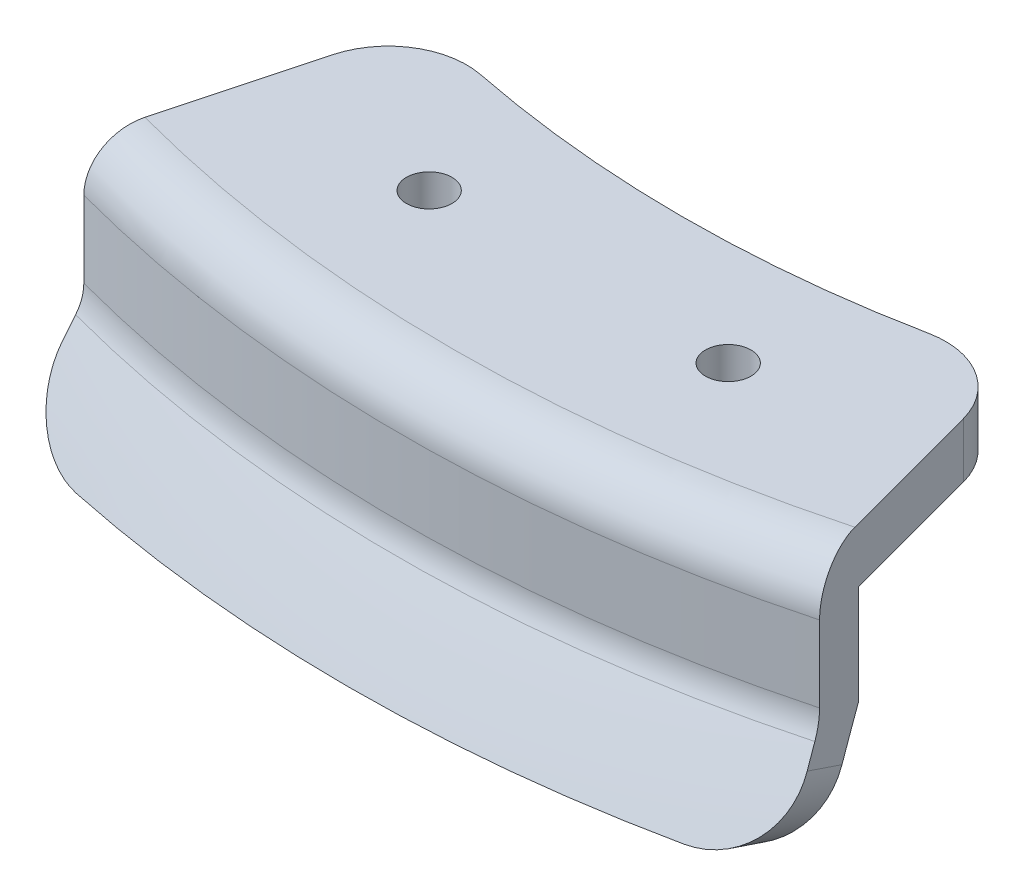
SolidWorks part; units mm, degrees
material "Polyether Polyol"
ref_plane "Front Plane" through (0, 0, 0) normal (0, 0, 1) x (1, 0, 0)
ref_plane "Top Plane" through (0, 0, 0) normal (0, 1, 0) x (1, 0, 0)
ref_plane "Right Plane" through (0, 0, 0) normal (1, 0, 0) x (0, 0, -1)
sketch "Sketch2" plane through (0, 0, 0) normal (1, 0, 0) x (0, 0, -1)
  line L0 (-174.1012, 207.3685) -> (-174.1012, 194.6685) construction
  line L1 (-188.0743, 183.7605) -> (-181.8111, 180.6344) construction
  line L2 (-181.1012, 214.3685) -> (-181.1012, 196.5948) construction
  line L3 (-181.1012, 214.3685) -> (-145.5262, 214.3685) construction
  line L4 (-145.5262, 214.3685) -> (-145.5262, 207.3685) construction
  line L5 (-145.5262, 207.3685) -> (-174.1012, 207.3685) construction
  line L12 (0, 89.8878) -> (0, 207.3685) construction
  line L13 (-174.1012, 207.3685) -> (-174.1012, 194.6685)
  line L14 (-188.0743, 183.7605) -> (-181.8111, 180.6344)
  line L15 (-181.1012, 214.3685) -> (-181.1012, 196.5948)
  line L16 (-181.1012, 214.3685) -> (-145.5262, 214.3685)
  line L17 (-145.5262, 214.3685) -> (-145.5262, 207.3685)
  line L18 (-145.5262, 207.3685) -> (-174.1012, 207.3685)
  arc A0 (-174.1012, 194.6685) -> (-181.8111, 180.6344) centre (0, 89.8878) ccw construction
  arc A1 (-181.1012, 196.5948) -> (-188.0743, 183.7605) centre (0, 89.8878) ccw construction
  arc A4 (-174.1012, 194.6685) -> (-181.8111, 180.6344) centre (0, 89.8878) ccw
  arc A5 (-181.1012, 196.5948) -> (-188.0743, 183.7605) centre (0, 89.8878) ccw
  point P0 (0, 92.6056)
revolve "Revolve1" add sketch "Sketch2" angle 30 mid plane about L12
fillet "Fillet1" radius 6.35 2 edges at (0, 196.5948, 181.1012) (0, 214.3685, 181.1012)
sketch "Sketch3" plane through (0, 214.3685, 0) normal (0, -1, 0) x (1, 0, 0)
  circle A2 centre (-19.05, 158.75) radius 3.5719 construction
  circle A3 centre (19.05, 158.75) radius 3.5719 construction
  circle A4 centre (19.05, 158.75) radius 2.9
  circle A5 centre (-19.05, 158.75) radius 2.9
  point P1 (-184.6202, 92.3675)
  point P3 (-183.1361, 81.4842)
  point P8 (-19.05, 158.75)
  point P10 (19.05, 158.75)
  dimension "D1" = 5.8
extrude "Cut-Extrude1" cut sketch "Sketch3" along normal through all contours A4 | A5 region at (19.05, 214.3685, 158.75) region at (-19.05, 214.3685, 158.75)
sketch "Sketch4" plane through (0, 214.3685, 0) normal (0, 1, 0) x (1, 0, 0)
  line L1 (-140.5675, 37.665) -> (-215.4275, 37.665)
  line L2 (-140.5675, 37.665) -> (-140.5675, -37.665)
  line L3 (-140.5675, -37.665) -> (-215.4275, -37.665)
  line L4 (-215.4275, 37.665) -> (-215.4275, -37.665)
extrude "Cut-Extrude2" cut sketch "Sketch4" against normal through all flip side to cut rebuild error yes
fillet "Fillet2" radius 10 4 edges at (-47.8667, 182.1975, 178.6409) (47.8667, 182.1975, 178.6409) (-37.665, 210.8685, 140.5675) (37.665, 210.8685, 140.5675)
sketch "Sketch5" plane through (0, 0, 0) normal (0, 0, 1) x (1, 0, 0)
  line L0 (0, 89.8878) -> (-181.0525, 182.1386) construction
  line L1 (0, 89.8878) -> (0, 207.3685) construction
  arc A1 (-174.1012, 194.6685) -> (146.7612, 230.4274) centre (0, 89.8878) ccw construction
  dimension "D1" = 63
ref_plane "Plane1" through (36.3604, 71.3612, 0) normal (0.454, 0.891, 0) x (-0.891, 0.454, 0)
sketch "Sketch6" plane through (36.3604, 71.3612, 0) normal (0.454, 0.891, 0) x (-0.891, 0.454, 0)
  line L0 (216.8377, 18.9708) -> (270.6406, 23.678) construction
  line L1 (40.8082, 0) -> (244.0082, 0) construction
  line L2 (216.8377, 18.9708) -> (271.2422, 23.7306)
  line L3 (216.8377, 18.9708) -> (216.5849, 21.8598)
  line L4 (271.2422, 23.7306) -> (270.9894, 26.6196)
  line L5 (216.5849, 21.8598) -> (270.9894, 26.6196)
  dimension "D1" = 5
  dimension "D2" = 2.9
revolve "Cut-Revolve1" cut sketch "Sketch6" angle 360 about L0 rebuild error yes
mirror "Mirror1" about plane through (0, 0, 0) normal (0, 0, 1) rebuild error yes
